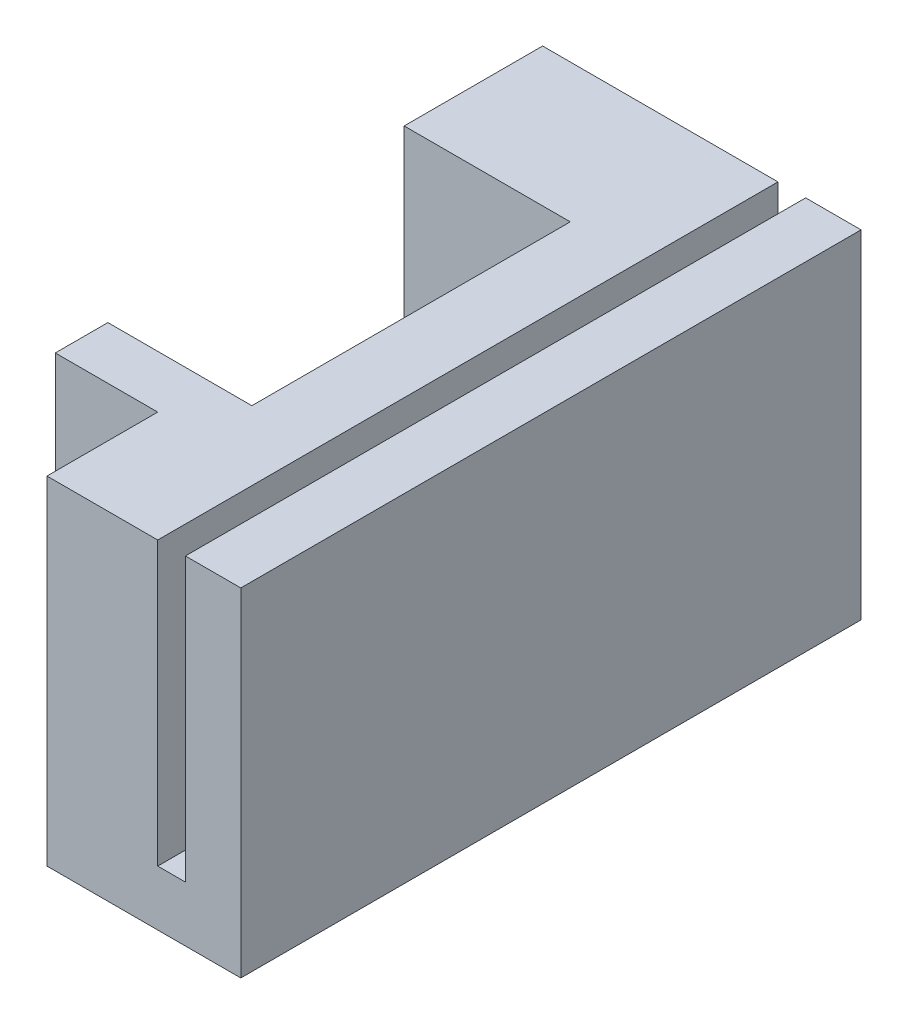
SolidWorks part; units mm, degrees
ref_plane "Front Plane" through (0, 0, 0) normal (0, 0, 1) x (1, 0, 0)
ref_plane "Top Plane" through (0, 0, 0) normal (0, 1, 0) x (1, 0, 0)
ref_plane "Right Plane" through (0, 0, 0) normal (1, 0, 0) x (0, 0, -1)
sketch "Sketch1" plane through (0, 0, 0) normal (0, 1, 0) x (1, 0, 0)
  line L0 (0, 0) -> (6, 0)
  line L1 (6, 0) -> (6, -11.5)
  line L2 (6, -11.5) -> (0.8, -11.5)
  line L3 (0.8, -11.5) -> (0.8, -13.4)
  line L4 (0.8, -13.4) -> (4.5, -13.4)
  line L6 (4.5, -17.4) -> (4.5, -13.4)
  line L8 (9.5, -17.4) -> (9.5, 5)
  line L9 (9.5, 5) -> (0, 5)
  line L10 (0, 5) -> (0, 0)
  line L11 (4.5, -17.4) -> (9.5, -17.4)
  line L12 (9.5, 5) -> (8.5, 5)
  line L13 (8.5, 5) -> (8.5, -17.4)
  line L14 (8.5, -17.4) -> (9.5, -17.4)
  line L15 (8.5, -17.4) -> (11.5, -17.4)
  line L16 (11.5, -17.4) -> (11.5, 5)
  line L17 (8.5, 5) -> (11.5, 5)
  point P8 (0.8, -12.45)
  point P14 (0, 2.5)
  point P17 (4.5, -15.4)
  dimension "D1" = 0.8
  dimension "D2" = 11.5
  dimension "D3" = 1
  dimension "D4" = 1.9
  dimension "D5" = 5
  dimension "D6" = 4
  dimension "D7" = 6
  dimension "D8" = 2.5
  dimension "D9" = 22.4
  dimension "D10" = 7
extrude "Boss-Extrude1" add sketch "Sketch1" along normal blind 12.2 contours L13 L9 L10 L0 L1 L2 L3 L4 L6 L11 | L17 L8 L15 L16 region at (0.2396, 0, -2.5) region at (10.5, 0, 6.2)
extrude "Boss-Extrude2" add sketch "Sketch1<4>" along normal blind 2 contours L9 L13 L11 L8 region at (9, 0, 6.2)
sketch "Sketch1<4>" plane through (0, 0, 0) normal (0, 1, 0) x (1, 0, 0) same geometry as "Sketch1"
